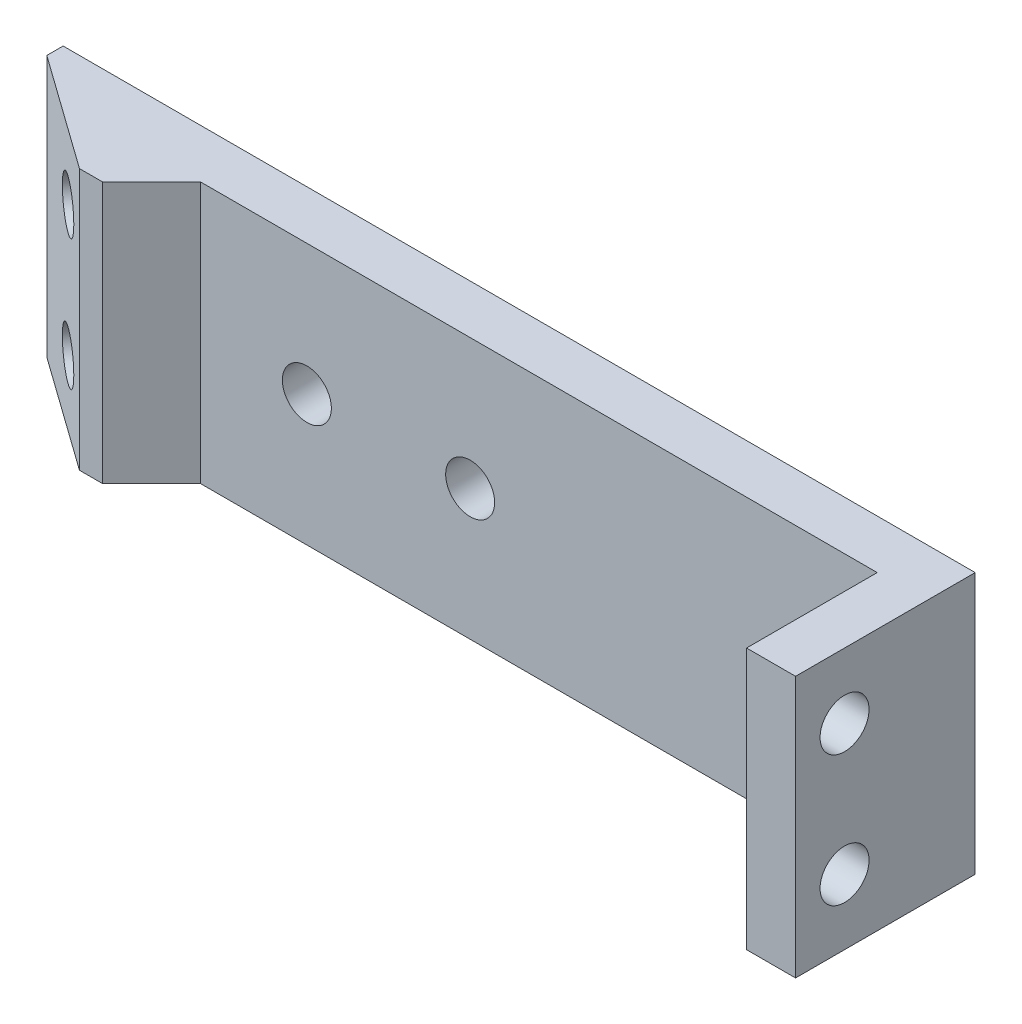
SolidWorks part; units mm, degrees
ref_plane "Front Plane" through (0, 0, 0) normal (0, 0, 1) x (1, 0, 0)
ref_plane "Top Plane" through (0, 0, 0) normal (0, 1, 0) x (1, 0, 0)
ref_plane "Right Plane" through (0, 0, 0) normal (1, 0, 0) x (0, 0, -1)
sketch "Sketch1" plane through (0, 0, 0) normal (0, 0, 1) x (1, 0, 0)
  line L1 (-27.925, -8) -> (27.925, -8)
  line L2 (-27.925, -8) -> (-27.925, 8)
  line L3 (-27.925, 8) -> (27.925, 8)
  line L4 (27.925, -8) -> (27.925, 8)
  line L5 (-27.925, -8) -> (27.925, 8) construction
  line L6 (-27.925, 8) -> (27.925, -8) construction
  point P0 (0, 0)
  dimension "D1" = 55.85
  dimension "D2" = 16
extrude "Boss-Extrude1" add sketch "Sketch1" along normal blind 3
sketch "Sketch2" plane through (0, 0, 3) normal (0, 0, 1) x (1, 0, 0)
  line L0 (-27.925, -8) -> (27.925, -8) construction
  line L1 (-27.925, 8) -> (-19.525, 8)
  line L2 (-27.925, 8) -> (-27.925, -8)
  line L3 (-27.925, -8) -> (-19.525, -8)
  line L4 (-19.525, 8) -> (-19.525, -8)
  dimension "D1" = 8.4
extrude "Boss-Extrude2" add sketch "Sketch2" along normal blind 3
chamfer "Chamfer1" distance 5 distance2 7 1 edges at (-27.925, 0, 6) first distance on face at (-27.925, 0, 3)
sketch "Sketch3" plane through (-9.9071, 0, 13.8699) normal (-0.5812, 0, 0.8137) x (0.8137, 0, 0.5812)
  line L0 (-22.1423, 8) -> (-13.5399, 8) construction
  line L1 (-13.5399, -8) -> (-22.1423, -8) construction
  line L2 (-13.5399, 8) -> (-13.5399, -8) construction
  circle A0 centre (-16.5399, 4) radius 1.5
  circle A1 centre (-16.5399, -4) radius 1.5
  dimension "D1" = 3
  dimension "D2" = 3
  dimension "D3" = 4
  dimension "D4" = 4
  dimension "D6" = 3
  dimension "D5" = 3
extrude "Cut-Extrude1" cut sketch "Sketch3" against normal blind 3
chamfer "Chamfer2" distance 3 angle 45 1 edges at (-19.525, 0, 3)
sketch "Sketch4" plane through (-9.9071, 0, 13.8699) normal (-0.5812, 0, 0.8137) x (0.8137, 0, 0.5812)
  line L1 (-13.3645, 4) -> (-14.9522, 6.75)
  line L2 (-14.9522, 6.75) -> (-18.1277, 6.75)
  line L3 (-18.1277, 6.75) -> (-19.7154, 4)
  line L4 (-19.7154, 4) -> (-18.1277, 1.25)
  line L5 (-18.1277, 1.25) -> (-14.9522, 1.25)
  line L6 (-14.9522, 1.25) -> (-13.3645, 4)
  line L7 (-13.3645, -4) -> (-14.9522, -1.25)
  line L8 (-14.9522, -1.25) -> (-18.1277, -1.25)
  line L9 (-18.1277, -1.25) -> (-19.7154, -4)
  line L10 (-19.7154, -4) -> (-18.1277, -6.75)
  line L11 (-18.1277, -6.75) -> (-14.9522, -6.75)
  line L12 (-14.9522, -6.75) -> (-13.3645, -4)
  circle A0 centre (-16.5399, 4) radius 2.75 construction
  circle A1 centre (-16.5399, -4) radius 2.75 construction
  dimension "D1" = 5.5
  dimension "D2" = 5.5
extrude "Cut-Extrude2" cut sketch "Sketch4" against normal blind 8 from offset 3 offset against normal yes
sketch "Sketch5" plane through (0, 0, 3) normal (0, 0, 1) x (1, 0, 0)
  line L0 (-16.525, -8) -> (27.925, -8) construction
  line L1 (27.925, 8) -> (24.925, 8)
  line L2 (27.925, 8) -> (27.925, -8)
  line L3 (27.925, -8) -> (24.925, -8)
  line L4 (24.925, 8) -> (24.925, -8)
  dimension "D1" = 3
extrude "Boss-Extrude3" add sketch "Sketch5" along normal blind 8
sketch "Sketch6" plane through (27.925, 0, 0) normal (1, 0, 0) x (0, 0, -1)
  line L0 (-11, -8) -> (-11, 8) construction
  line L1 (-11, 8) -> (0, 8) construction
  line L2 (-11, -8) -> (0, -8) construction
  circle A0 centre (-8, 4) radius 1.5
  circle A1 centre (-8, -4) radius 1.5
  dimension "D1" = 3
  dimension "D2" = 3
  dimension "D3" = 3
  dimension "D4" = 3
  dimension "D5" = 4
  dimension "D6" = 4
extrude "Cut-Extrude3" cut sketch "Sketch6" against normal blind 8
sketch "Sketch7" plane through (0, 0, 0) normal (0, 0, -1) x (-1, 0, 0)
  circle A0 centre (10, 0) radius 1.5
  dimension "D1" = 3
  dimension "D2" = 10
extrude "Cut-Extrude4" cut sketch "Sketch7" against normal blind 10
sketch "Sketch8" plane through (0, 0, 3) normal (0, 0, 1) x (1, 0, 0)
  circle A0 centre (0, 0) radius 1.5
  circle A1 centre (-10, 0) radius 1.5 construction
  dimension "D1" = 3
  dimension "D2" = 10
extrude "Cut-Extrude5" cut sketch "Sketch8" against normal blind 10
